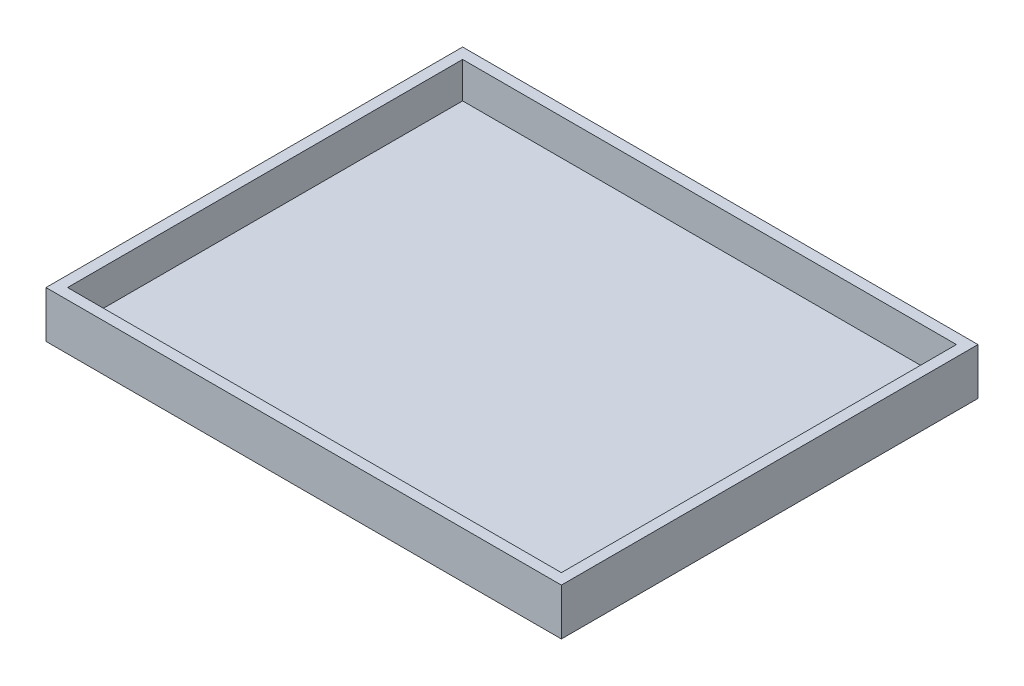
SolidWorks part; units mm, degrees
ref_plane "Front Plane" through (0, 0, 0) normal (0, 0, 1) x (1, 0, 0)
ref_plane "Top Plane" through (0, 0, 0) normal (0, 1, 0) x (1, 0, 0)
ref_plane "Right Plane" through (0, 0, 0) normal (1, 0, 0) x (0, 0, -1)
sketch "Sketch1" plane through (0, 0, 0) normal (0, 1, 0) x (1, 0, 0)
  line L1 (0, 0) -> (55, 0)
  line L2 (0, 0) -> (0, -44)
  line L3 (0, -44) -> (55, -44)
  line L4 (55, 0) -> (55, -44)
  point P4 (0, 0)
  point P5 (55, -28.4294)
  dimension "D1" = 55
  dimension "D2" = 44
extrude "Boss-Extrude1" add sketch "Sketch1" along normal blind 4
shell "Shell1" thickness 1.2 removed face at (27.5, 4, 22) outward yes
